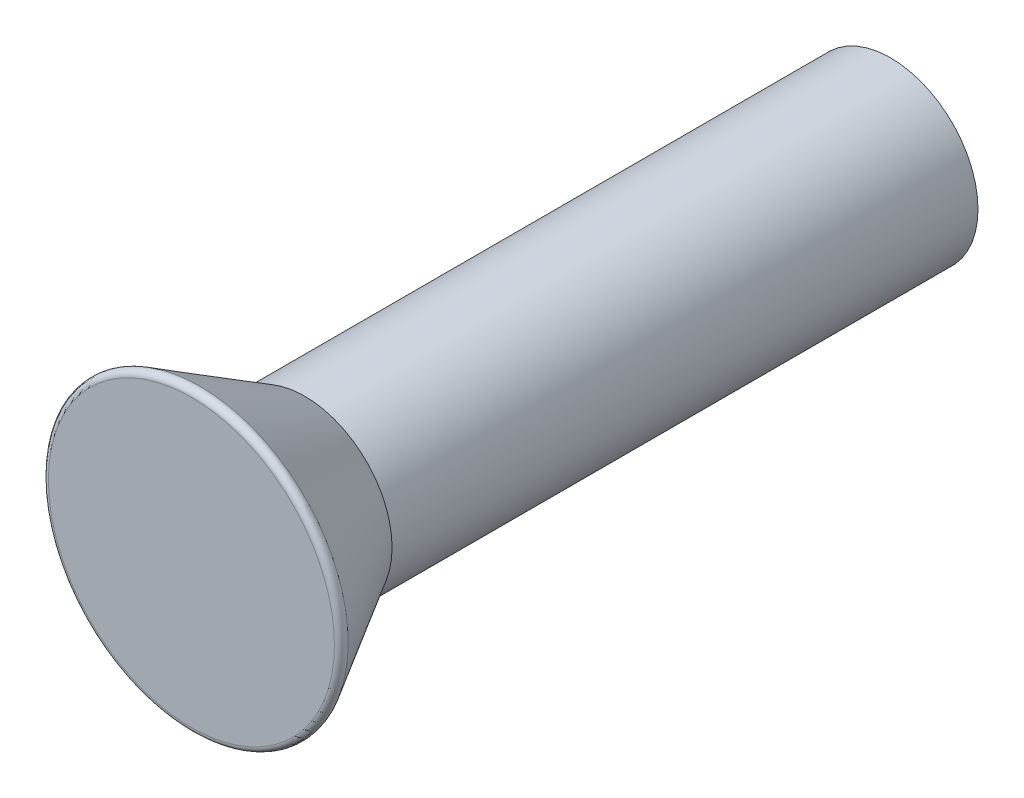
SolidWorks part; units mm, degrees
ref_plane "Front Plane" through (0, 0, 0) normal (0, 0, 1) x (1, 0, 0)
ref_plane "Top Plane" through (0, 0, 0) normal (0, 1, 0) x (1, 0, 0)
ref_plane "Right Plane" through (0, 0, 0) normal (1, 0, 0) x (0, 0, -1)
sketch "BaseBodySke" plane through (0, 0, 0) normal (0, 1, 0) x (1, 0, 0)
  line L0 (0, 0) -> (-5.5626, 0)
  line L1 (0, 0) -> (0, 32.7778) construction
  line L2 (0, 0) -> (0, 25.4)
  line L3 (0, 25.4) -> (-3.175, 25.4)
  line L4 (-3.175, 4.1148) -> (-3.175, 25.4)
  line L5 (-5.5626, 25.4) -> (-5.5626, 0) construction
  line L6 (-5.5626, -4.1148) -> (-5.5626, 0) construction
  line L7 (-5.5626, 0) -> (-3.175, 4.1148)
  line L9 (-3.175, 4.1148) -> (-3.175, 0) construction
  dimension "Head_Diameter" = 11.1252
  dimension "Diameter" = 6.35
revolve "BaseBody" add sketch "BaseBodySke" angle 360 about L1
fillet "Fillet" radius 0.2117 1 edges at (5.5626, 0, 0)
equation "\"D1@Fillet\" = \"Diameter@BaseBodySke\" / 30"
